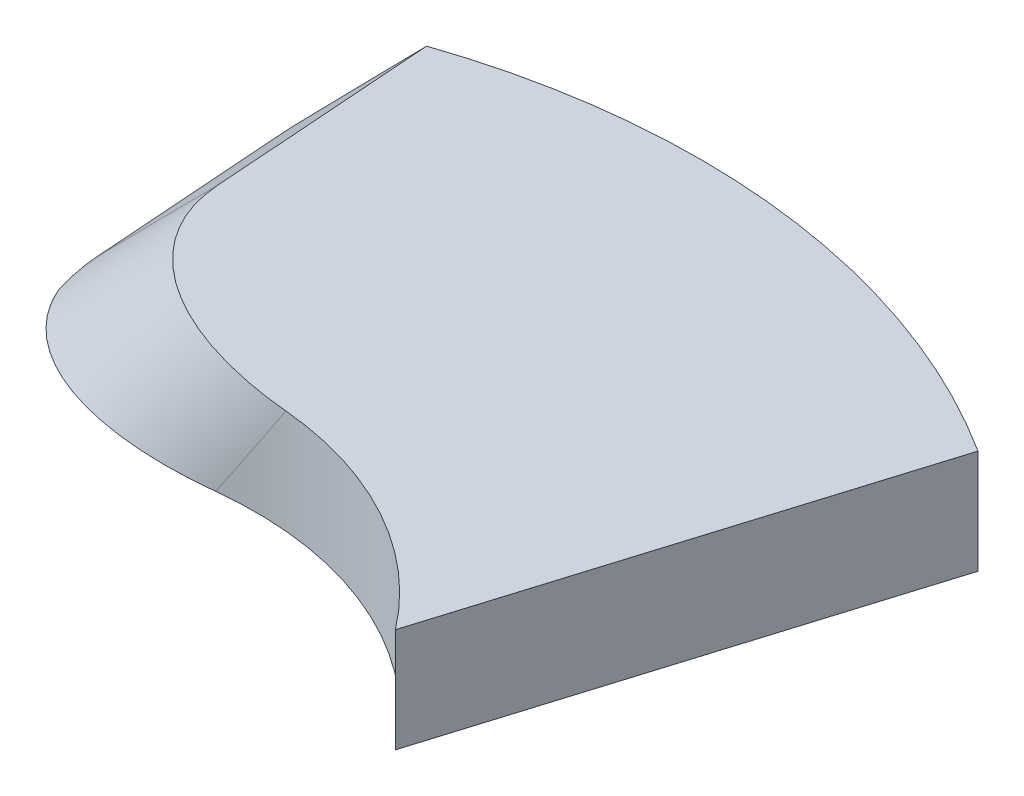
SolidWorks part; units mm, degrees
ref_plane "Front Plane" through (0, 0, 0) normal (0, 0, 1) x (1, 0, 0)
ref_plane "Top Plane" through (0, 0, 0) normal (0, 1, 0) x (1, 0, 0)
ref_plane "Right Plane" through (0, 0, 0) normal (1, 0, 0) x (0, 0, -1)
sketch "Sketch1" plane through (0, 0, 0) normal (0, 1, 0) x (1, 0, 0)
  line L0 (-8.5429, 4.8586) -> (-9.53, 18.7131)
  line L1 (7.3406, 4.8586) -> (11.2785, 17.7143)
  arc A0 (11.2785, 17.7143) -> (-9.53, 18.7131) centre (0, 0) ccw
  arc A2 (-8.5429, 4.8586) -> (7.3406, 4.8586) centre (-0.6012, -1.2183) cw
  point P1 (-5.2473, 6.5155)
  point P8 (5.1875, 6.5155)
  point P9 (-8.5429, 4.8586)
  point P10 (7.3406, 4.8586)
  dimension "D4" = 10
extrude "Boss-Extrude1" add sketch "Sketch1" along normal blind 3
ref_plane "Plane1" through (-5.5739, 5.588, 0.3971) normal (-0.7053, 0.7071, 0.0502) x (0.0711, 0, 0.9975)
sketch "Sketch2" plane through (-5.5739, 5.588, 0.3971) normal (-0.7053, 0.7071, 0.0502) x (0.0711, 0, 0.9975)
  line L0 (-19.343, -3.66) -> (-5.4534, -3.66) construction
  line L1 (-20.8982, -7.0868) -> (-3.8982, -7.0868)
  line L2 (-20.8982, -7.0868) -> (-20.8982, -0.2333)
  line L3 (-20.8982, -0.2333) -> (-3.8982, -0.2333)
  line L4 (-3.8982, -7.0868) -> (-3.8982, -0.2333)
  line L5 (-20.8982, -7.0868) -> (-3.8982, -0.2333) construction
  line L6 (-20.8982, -0.2333) -> (-3.8982, -7.0868) construction
  point P0 (-12.3982, -3.66)
  dimension "D1" = 17
extrude "Cut-Extrude1" cut sketch "Sketch2" against normal blind 2
fillet "Fillet1" radius 5 1 edges at (-7.3207, 1.4851, -6.1877)
